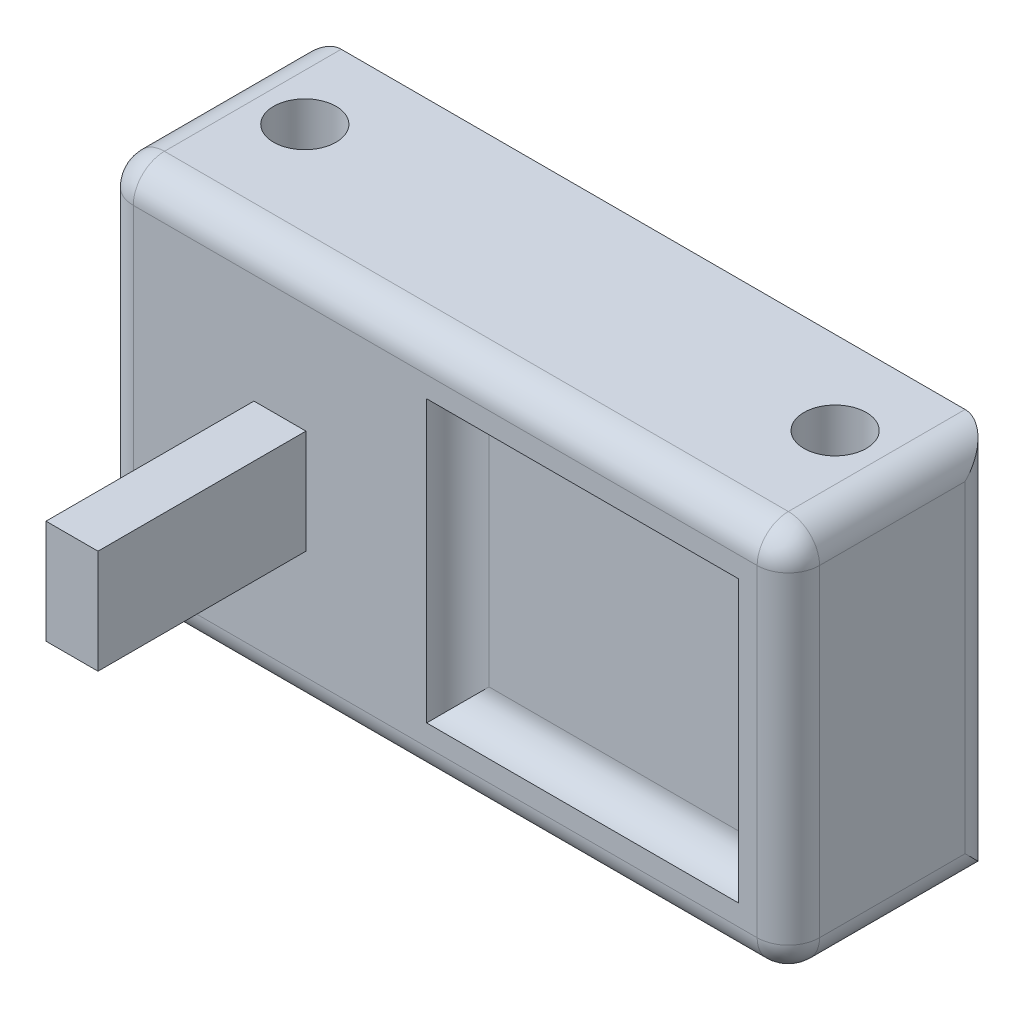
SolidWorks part; units mm, degrees
ref_plane "Ebene vorne" through (0, 0, 0) normal (0, 0, 1) x (1, 0, 0)
ref_plane "Ebene oben" through (0, 0, 0) normal (0, 1, 0) x (1, 0, 0)
ref_plane "Ebene rechts" through (0, 0, 0) normal (1, 0, 0) x (0, 0, -1)
sketch "Skizze1" plane through (0, 0, 0) normal (0, 0, 1) x (1, 0, 0)
  line L1 (-378.4567, 175.3743) -> (281.5433, 175.3743)
  line L2 (-378.4567, 175.3743) -> (-378.4567, -194.6257)
  line L3 (-378.4567, -194.6257) -> (281.5433, -194.6257)
  line L4 (281.5433, 175.3743) -> (281.5433, -194.6257)
  dimension "D1" = 660
  dimension "D2" = 370
extrude "Aufsatz-Linear austragen1" add sketch "Skizze1" along normal blind 200
sketch "Skizze2" plane through (0, -194.6257, 0) normal (0, -1, 0) x (1, 0, 0)
  line L0 (-378.4567, 200) -> (-378.4567, 0) construction
  line L1 (-378.4567, 0) -> (281.5433, 0) construction
  circle A0 centre (-303.4567, 80) radius 30
  circle A1 centre (206.5433, 80) radius 30
  dimension "D1" = 510
  dimension "D2" = 75
  dimension "D3" = 80
extrude "Schnitt-Linear austragen1" cut sketch "Skizze2" against normal through all
fillet "Verrundung1" radius 30 10 edges at (-378.4567, 175.3743, 100) (-378.4567, -9.6257, 200) (-378.4567, -194.6257, 100) (-378.4567, -9.6257, 0) (281.5433, -194.6257, 100) (281.5433, 175.3743, 100) (-48.4567, -194.6257, 200) (-48.4567, 175.3743, 200) (281.5433, -9.6257, 0) (281.5433, -9.6257, 200)
sketch "Skizze3" plane through (0, 0, 200) normal (0, 0, 1) x (1, 0, 0)
  line L0 (251.5433, -164.6257) -> (251.5433, 145.3743) construction
  line L1 (-66.2824, 125.3743) -> (233.7176, 125.3743)
  line L2 (-66.2824, 125.3743) -> (-66.2824, -144.6257)
  line L3 (-66.2824, -144.6257) -> (233.7176, -144.6257)
  line L4 (233.7176, 125.3743) -> (233.7176, -144.6257)
  line L5 (251.5433, 145.3743) -> (-348.4567, 145.3743) construction
  line L6 (-348.4567, -164.6257) -> (251.5433, -164.6257) construction
  dimension "D1" = 17.8257
  dimension "D2" = 20
  dimension "D3" = 20
  dimension "D4" = 300
extrude "Schnitt-Linear austragen2" cut sketch "Skizze3" against normal blind 30
fillet "Verrundung2" radius 30 4 edges at (233.7176, -9.6257, 170) (83.7176, -144.6257, 170) (-66.2824, -9.6257, 170) (83.7176, 125.3743, 170)
sketch "Skizze5" plane through (0, 0, 200) normal (0, 0, 1) x (1, 0, 0)
  line L0 (-348.4567, -9.6257) -> (-66.2824, -9.6257) construction
  line L1 (-348.4567, 145.3743) -> (-348.4567, -164.6257) construction
  line L2 (-66.2824, 125.3743) -> (-66.2824, -144.6257) construction
  line L4 (-232.3695, -59.6257) -> (-182.3695, -59.6257)
  line L5 (-232.3695, -59.6257) -> (-232.3695, 40.3743)
  line L6 (-232.3695, 40.3743) -> (-182.3695, 40.3743)
  line L7 (-182.3695, -59.6257) -> (-182.3695, 40.3743)
  line L8 (-232.3695, -59.6257) -> (-182.3695, 40.3743) construction
  line L9 (-232.3695, 40.3743) -> (-182.3695, -59.6257) construction
  point P6 (-207.3695, -9.6257)
  dimension "D1" = 100
  dimension "D2" = 50
extrude "Aufsatz-Linear austragen2" add sketch "Skizze5" along normal blind 200
